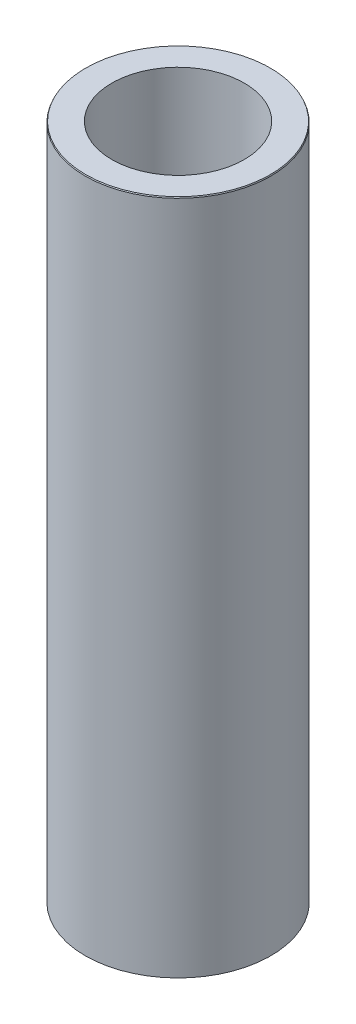
SolidWorks part; units mm, degrees
ref_plane "Front Plane" through (0, 0, 0) normal (0, 0, 1) x (1, 0, 0)
ref_plane "Top Plane" through (0, 0, 0) normal (0, 1, 0) x (1, 0, 0)
ref_plane "Right Plane" through (0, 0, 0) normal (1, 0, 0) x (0, 0, -1)
sketch "Sketch1" plane through (0, 0, 0) normal (0, 1, 0) x (1, 0, 0)
  circle A0 centre (0, 0) radius 55
  dimension "SHAFT_OD" = 110
extrude "Boss-Extrude1" add sketch "Sketch1" along normal blind 401.1843
sketch "Sketch2" plane through (0, 0, 0) normal (0, 1, 0) x (1, 0, 0)
  circle A0 centre (0, 0) radius 39.2815
  dimension "BORE_D" = 78.5631
extrude "Cut-Extrude1" cut sketch "Sketch2" along normal through all
chamfer "Chamfer1" distance 0.6525 angle 23.013 2 edges at (0, 401.1843, 55) (0, 0, 55) first distance on face at (0, 401.1843, 55) first distance on face at (0, 0, 39.2815)
